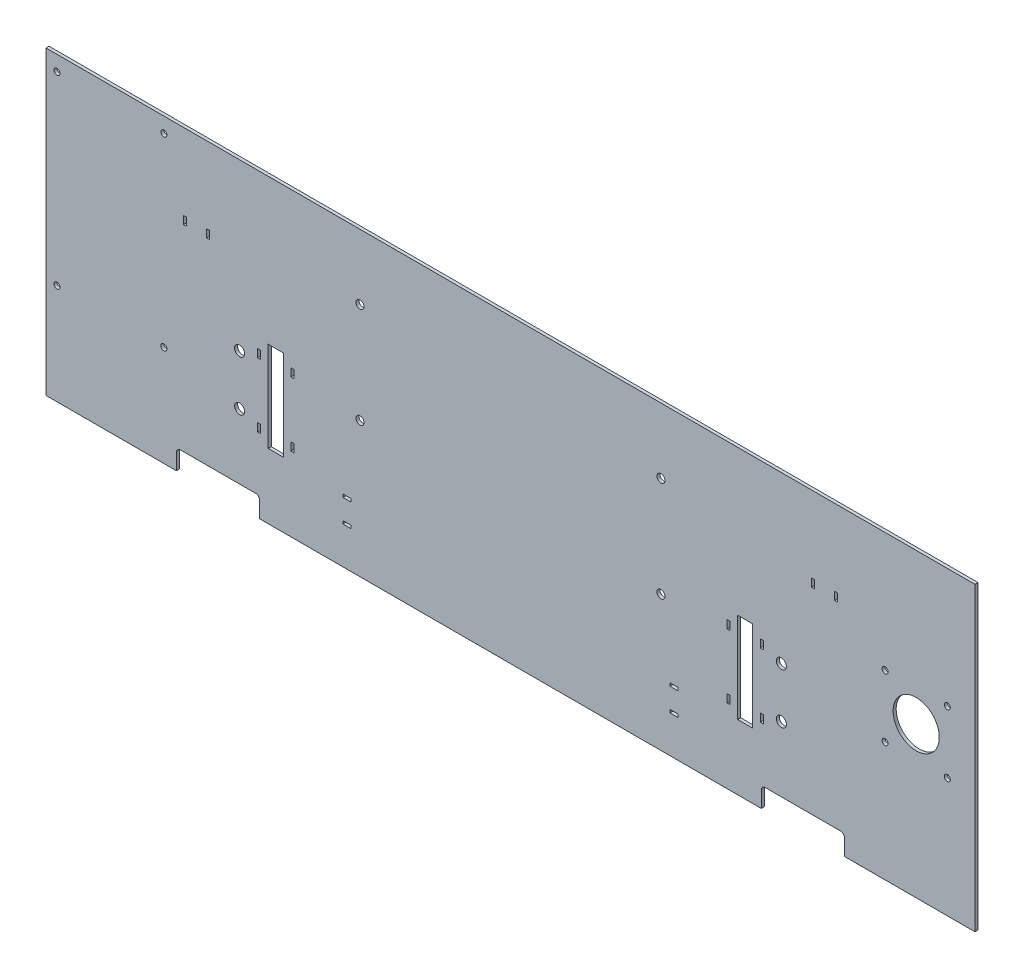
SolidWorks part; units mm, degrees
material "5052-H32"
ref_plane "Front Plane" through (0, 0, 0) normal (0, 0, 1) x (1, 0, 0)
ref_plane "Top Plane" through (0, 0, 0) normal (0, 1, 0) x (1, 0, 0)
ref_plane "Right Plane" through (0, 0, 0) normal (1, 0, 0) x (0, 0, -1)
sketch "Sketch1" plane through (0, 0, 0) normal (0, 0, 1) x (1, 0, 0)
  line L1 (-231.5, 75) -> (231.5, 75)
  line L2 (-231.5, 75) -> (-231.5, -75)
  line L3 (-231.5, -75) -> (231.5, -75)
  line L4 (231.5, 75) -> (231.5, -75)
  line L5 (0, -75) -> (0, 75) construction
  line L6 (-231.5, 0) -> (231.5, 0) construction
  point P480 (0, 0)
  dimension "D1" = 463
  dimension "D2" = 150
base flange "Base-Flange1" sketch "Sketch1" thickness 1.5189 reverse thickness direction no parameters "D1"=0.381
sketch "Sketch48" plane through (0, 0, -1.5189) normal (0, 0, -1) x (-1, 0, 0)
  line L0 (-231.119, 75) -> (-231.119, -75) construction
  line L1 (-231.119, 73.1001) -> (231.119, 73.1001) construction
  line L2 (0, 0) -> (-50000, 0) construction
  line L3 (0, 0) -> (0, -50000) construction
  line L4 (120.75, -42.5) -> (113.25, -42.5)
  line L5 (-120.75, 2.5) -> (-113.25, 2.5)
  line L6 (-120.75, 2.5) -> (-120.75, -42.5)
  line L7 (-120.75, -42.5) -> (-113.25, -42.5)
  line L8 (-113.25, 15) -> (-120.75, 15) construction
  line L9 (-113.25, -9) -> (-113.25, 15) construction
  line L10 (-120.75, -9) -> (-113.25, -9) construction
  line L11 (-120.75, 15) -> (-120.75, -9) construction
  line L12 (-113.25, 2.5) -> (-113.25, -42.5)
  line L13 (-120.75, 2.5) -> (-113.25, -42.5) construction
  line L14 (-120.75, -42.5) -> (-113.25, 2.5) construction
  line L15 (113.25, 2.5) -> (113.25, -42.5)
  line L16 (-120.75, -55) -> (-113.25, -55) construction
  line L17 (-120.75, -31) -> (-120.75, -55) construction
  line L18 (-113.25, -31) -> (-120.75, -31) construction
  line L19 (-113.25, -55) -> (-113.25, -31) construction
  line L20 (120.75, -42.5) -> (113.25, 2.5) construction
  line L21 (120.75, 2.5) -> (113.25, -42.5) construction
  line L22 (120.75, 2.5) -> (120.75, -42.5)
  line L23 (120.75, 2.5) -> (113.25, 2.5)
  line L24 (-109.5, -6) -> (-108, -6)
  line L25 (-109.5, -2) -> (-109.5, -6)
  line L26 (-108, -2) -> (-109.5, -2)
  line L27 (-108, -6) -> (-108, -2)
  line L32 (-124.5, 8) -> (-124.5, 12) construction
  line L33 (-126, 8) -> (-124.5, 8) construction
  line L34 (-126, 12) -> (-126, 8) construction
  line L35 (-124.5, 12) -> (-126, 12) construction
  line L40 (-126, -2) -> (-126, -6)
  line L41 (-124.5, -2) -> (-126, -2)
  line L42 (-124.5, -6) -> (-124.5, -2)
  line L43 (-126, -6) -> (-124.5, -6)
  line L48 (-109.5, 12) -> (-109.5, 8) construction
  line L49 (-108, 12) -> (-109.5, 12) construction
  line L50 (-108, 8) -> (-108, 12) construction
  line L51 (-109.5, 8) -> (-108, 8) construction
  line L56 (-124.5, -38) -> (-124.5, -34)
  line L57 (-126, -38) -> (-124.5, -38)
  line L58 (-126, -34) -> (-126, -38)
  line L59 (-124.5, -34) -> (-126, -34)
  line L64 (-109.5, -34) -> (-109.5, -38)
  line L65 (-108, -34) -> (-109.5, -34)
  line L66 (-108, -38) -> (-108, -34)
  line L67 (-109.5, -38) -> (-108, -38)
  line L72 (-109.5, -52) -> (-108, -52) construction
  line L73 (-109.5, -48) -> (-109.5, -52) construction
  line L74 (-108, -48) -> (-109.5, -48) construction
  line L75 (-108, -52) -> (-108, -48) construction
  line L80 (-126, -48) -> (-126, -52) construction
  line L81 (-124.5, -48) -> (-126, -48) construction
  line L82 (-124.5, -52) -> (-124.5, -48) construction
  line L83 (-126, -52) -> (-124.5, -52) construction
  line L88 (-79.5, -45) -> (-79.5, -43.5)
  line L89 (-83.5, -45) -> (-79.5, -45)
  line L90 (-83.5, -43.5) -> (-83.5, -45)
  line L91 (-79.5, -43.5) -> (-83.5, -43.5)
  line L96 (-79.5, -56.5) -> (-79.5, -55)
  line L97 (-83.5, -56.5) -> (-79.5, -56.5)
  line L98 (-83.5, -55) -> (-83.5, -56.5)
  line L99 (-79.5, -55) -> (-83.5, -55)
  line L104 (-151.5, 33) -> (-150, 33)
  line L105 (-151.5, 37) -> (-151.5, 33)
  line L106 (-150, 37) -> (-151.5, 37)
  line L107 (-150, 33) -> (-150, 37)
  line L112 (-163, 33) -> (-161.5, 33)
  line L113 (-163, 37) -> (-163, 33)
  line L114 (-161.5, 37) -> (-163, 37)
  line L115 (-161.5, 33) -> (-161.5, 37)
  line L120 (113.25, 15) -> (113.25, -9) construction
  line L121 (120.75, 15) -> (113.25, 15) construction
  line L122 (120.75, -9) -> (120.75, 15) construction
  line L123 (113.25, -9) -> (120.75, -9) construction
  line L128 (113.25, -55) -> (120.75, -55) construction
  line L129 (113.25, -31) -> (113.25, -55) construction
  line L130 (120.75, -31) -> (113.25, -31) construction
  line L131 (120.75, -55) -> (120.75, -31) construction
  line L136 (124.5, -34) -> (124.5, -38)
  line L137 (126, -34) -> (124.5, -34)
  line L138 (126, -38) -> (126, -34)
  line L139 (124.5, -38) -> (126, -38)
  line L144 (108, -48) -> (108, -52) construction
  line L145 (109.5, -48) -> (108, -48) construction
  line L146 (109.5, -52) -> (109.5, -48) construction
  line L147 (108, -52) -> (109.5, -52) construction
  line L152 (109.5, -38) -> (109.5, -34)
  line L153 (108, -38) -> (109.5, -38)
  line L154 (108, -34) -> (108, -38)
  line L155 (109.5, -34) -> (108, -34)
  line L160 (124.5, -52) -> (126, -52) construction
  line L161 (124.5, -48) -> (124.5, -52) construction
  line L162 (126, -48) -> (124.5, -48) construction
  line L489 (126, -52) -> (126, -48) construction
  line L494 (83.5, -45) -> (83.5, -43.5)
  line L495 (79.5, -45) -> (83.5, -45)
  line L496 (79.5, -43.5) -> (79.5, -45)
  line L497 (83.5, -43.5) -> (79.5, -43.5)
  line L502 (83.5, -55) -> (79.5, -55)
  line L503 (83.5, -56.5) -> (83.5, -55)
  line L504 (79.5, -56.5) -> (83.5, -56.5)
  line L505 (79.5, -55) -> (79.5, -56.5)
  line L510 (163, 37) -> (161.5, 37)
  line L511 (163, 33) -> (163, 37)
  line L512 (161.5, 33) -> (163, 33)
  line L513 (161.5, 37) -> (161.5, 33)
  line L518 (150, 37) -> (150, 33)
  line L519 (151.5, 37) -> (150, 37)
  line L520 (151.5, 33) -> (151.5, 37)
  line L521 (150, 33) -> (151.5, 33)
  line L526 (109.5, 8) -> (109.5, 12) construction
  line L527 (108, 8) -> (109.5, 8) construction
  line L528 (108, 12) -> (108, 8) construction
  line L529 (109.5, 12) -> (108, 12) construction
  line L534 (108, -2) -> (108, -6)
  line L535 (109.5, -2) -> (108, -2)
  line L536 (109.5, -6) -> (109.5, -2)
  line L537 (108, -6) -> (109.5, -6)
  line L542 (124.5, -2) -> (124.5, -6)
  line L543 (126, -2) -> (124.5, -2)
  line L544 (126, -6) -> (126, -2)
  line L545 (124.5, -6) -> (126, -6)
  line L550 (126, 8) -> (126, 12) construction
  line L551 (124.5, 8) -> (126, 8) construction
  line L552 (124.5, 12) -> (124.5, 8) construction
  line L553 (126, 12) -> (124.5, 12) construction
  circle A2 centre (-186.715, -15.5) radius 1.5
  circle A4 centre (-186.715, 15.5) radius 1.5
  circle A6 centre (-217.715, 15.5) radius 1.5
  circle A17 centre (-202.215, 0) radius 11.5
  circle A24 centre (-217.715, -15.5) radius 1.5
  circle A26 centre (-135, -7.5) radius 2.5
  circle A28 centre (-135, -32.5) radius 2.5
  circle A30 centre (-75, -7.5) radius 2
  circle A32 centre (-75, 42.5) radius 2
  circle A34 centre (135, -32.5) radius 2.5
  circle A36 centre (135, -7.5) radius 2.5
  circle A38 centre (75, -7.5) radius 2
  circle A40 centre (75, 42.5) radius 2
  circle A42 centre (172.7419, -24.8359) radius 1.5
  circle A44 centre (226.0189, -24.8359) radius 1.5
  circle A46 centre (172.7419, 67.4811) radius 1.5
  circle A47 centre (226.0189, 67.4811) radius 1.5
  point P14 (-117, -20)
  dimension "D1" = 23
  dimension "D2" = 3
  dimension "D3" = 5
  dimension "D4" = 4
  dimension "D7" = 202.215
  dimension "D5" = 24
  dimension "D6" = 7.5
  dimension "D8" = 113.25
  dimension "D9" = 22
  dimension "D10" = 15
  dimension "D11" = 8
  dimension "D12" = 2
  dimension "D13" = 7.5
  dimension "D14" = 33
  dimension "D15" = 50
  dimension "D16" = 15.5
  dimension "D17" = 31
  dimension "D18" = 3
  dimension "D19" = 43.5
  dimension "D20" = 14
  dimension "D21" = 32.5
  dimension "D22" = 67.4811
  dimension "D23" = 92.317
  dimension "D24" = 4
  dimension "D25" = 1.5
  dimension "D26" = 75
  dimension "D27" = 79.5
  dimension "D28" = 3.75
  dimension "D29" = 113.25
  dimension "D30" = 15
  dimension "D31" = 135
  dimension "D32" = 150
  dimension "D33" = 11.5
  dimension "D34" = 172.7419
  dimension "D35" = 150
  dimension "D36" = 53.277
  dimension "D37" = 31
  dimension "D38" = 15.5
  dimension "D39" = 15
  dimension "D40" = 3.75
  dimension "D41" = 79.5
  dimension "D42" = 14.25
  dimension "D43" = 150
  dimension "D44" = 11.5
  dimension "D45" = 7.5
  dimension "D46" = 113.25
  dimension "D47" = 45
  dimension "D48" = 70
  dimension "D49" = 20
extrude "Cut-Extrude1" cut sketch "Sketch48" against normal blind 1.5189 contours A44 | A42 | L120 L123 L122 L121 | A36 | L550 L553 L552 L551 | L542 L545 L544 L543 | L534 L537 L536 L535 | L526 L529 L528 L527 | A34 | L136 L139 L138 L137 | L128 L131 L130 L129 | L152 L155 L154 L153 | L144 L147 L146 L145 | L160 L489 L162 L161 | L494 L497 L496 L495 | L502 L505 L504 L503 | L510 L513 L512 L511 | A40 | A38 | L88 L91 L90 L89 | L96 L99 L98 L97 | L16 L19 L18 L17 | L64 L67 L66 L65 | L72 L75 L74 L73 | L80 L83 L82 L81 | L56 L59 L58 L57 | A28 | A26 | A30 | A32 | L8 L11 L10 L9 | L40 L43 L42 L41 | L32 L35 L34 L33 | L48 L51 L50 L49 | L24 L27 L26 L25 | L112 L115 L114 L113 | L104 L107 L106 L105 | A4 | A2 | A24 | A6 | A17 | A47 | A46 | L12 L5 L6 L7 | L22 L23 L15 L4 | L520 L519 L518 L521 normal cut yes
sketch "Sketch50" plane through (0, 0, 0) normal (0, 0, 1) x (1, 0, 0)
  line L0 (125, -75) -> (166.5, -75)
  line L1 (-125, -75) -> (-166.5, -75)
  line L2 (0, 0) -> (0, -75) construction
  line L424 (-166.5, -75) -> (-166.5, -67)
  line L425 (-164.5, -65) -> (-127, -65)
  line L426 (-125, -67) -> (-125, -75)
  line L448 (125, -75) -> (125, -67)
  line L449 (127, -65) -> (164.5, -65)
  line L450 (166.5, -67) -> (166.5, -75)
  arc A17 (-164.5, -65) -> (-166.5, -67) centre (-164.5, -67) ccw
  arc A18 (-125, -67) -> (-127, -65) centre (-127, -67) ccw
  arc A19 (127, -65) -> (125, -67) centre (127, -67) ccw
  arc A20 (166.5, -67) -> (164.5, -65) centre (164.5, -67) ccw
  dimension "D4" = 2
  dimension "D1" = 41.5
  dimension "D2" = 125
  dimension "D3" = 10
  dimension "D5" = 125
  dimension "D6" = 75
extrude "Cut-Extrude3" cut sketch "Sketch50" against normal blind 10 contours L450 A20 L449 A19 L448 L0 | L426 A18 L425 A17 L424 L1
edge flange "Edge-Flange1" [suppressed] sketch "Sketch10" flange profiles "Sketch10", "Sketch11" flange angle 90 flange position material outside bend radius 0.381 thickness 1.5189
sketch "Sketch10" plane through (231.5, 0, 0) normal (1, 0, 0) x (0, 1, 0)
  line L2 (-75, 0) -> (-75, 425)
  line L3 (-75, 425) -> (75, 425)
  line L4 (75, 425) -> (75, 0)
  line L7 (-75, 0) -> (75, 0) construction
  line L8 (-75, 0) -> (75, 0)
sketch "Sketch11" plane through (-231.5, 0, 0) normal (-1, 0, 0) x (0, -1, 0)
  line L2 (-75, 0) -> (-75, 425)
  line L3 (-75, 425) -> (75, 425)
  line L4 (75, 425) -> (75, 0)
  line L5 (-75, 0) -> (75, 0) construction
  line L6 (-75, 0) -> (75, 0)
bend "EdgeBend1" bend radius 0.381 bend angle 90 parameters "D5"=1
bend "EdgeBend2" bend radius 0.381 bend angle 90 parameters "D5"=2, "D6"=10, "D7"=425
edge flange "Edge-Flange2" [suppressed] sketch "Sketch16" flange profiles "Sketch16", "Sketch17" flange angle 90 flange position material inside bend radius 0.381 thickness 1.5189
sketch "Sketch16" plane through (231.5, 0, 425) normal (0, 0, 1) x (0, 1, 0)
  line L0 (75, 0) -> (-75, 0) construction
  line L1 (75, 0) -> (-75, 0)
  line L2 (-75, 0) -> (-75, 231.3811)
  line L3 (-75, 231.3811) -> (75, 231.3811)
  line L4 (75, 231.3811) -> (75, 0)
sketch "Sketch17" plane through (-231.5, 0, 425) normal (0, 0, 1) x (0, -1, 0)
  line L0 (75, 0) -> (-75, 0) construction
  line L1 (75, 0) -> (-75, 0)
  line L2 (-75, 0) -> (-75, 231.3811)
  line L3 (-75, 231.3811) -> (75, 231.3811)
  line L4 (75, 231.3811) -> (75, 0)
bend "EdgeBend3" bend radius 0.381 bend angle 90 parameters "D5"=3
bend "EdgeBend4" bend radius 0.381 bend angle 90 parameters "D5"=4, "D6"=10, "D7"=232.9
sketch "Sketch49" [suppressed] plane through (233.0189, 0, 0) normal (1, 0, 0) x (0, 0, -1)
  line L2 (-425, 75) -> (-425, -75) construction
  line L3 (-378.715, 0) -> (-425, 0) construction
  line L4 (-408.715, 35) -> (-408.715, -35)
  line L5 (-378.715, -35) -> (-378.715, 35)
  arc A1 (-408.715, -35) -> (-378.715, -35) centre (-393.715, -35) ccw
  arc A4 (-408.715, -35) -> (-378.715, -35) centre (-393.715, -35) ccw
  arc A5 (-378.715, 35) -> (-408.715, 35) centre (-393.715, 35) ccw
  dimension "D3" = 70
  dimension "D1" = 16.285
  dimension "D2" = 30
extrude "Cut-Extrude2" [suppressed] cut sketch "Sketch49" against normal through all contours L5 A5 L4 A1 | L3 L5 A5 L4
edge flange "Edge-Flange3" [suppressed] sketch "Sketch38" flange profiles "Sketch38", "Sketch39", "Sketch40", "Sketch41", "Sketch42", "Sketch43", "Sketch44", "Sketch45", "Sketch46", "Sketch47" flange angle 90 flange position material inside bend radius 0.381 thickness 1.5189
sketch "Sketch38" plane through (0, 75, 423.4811) normal (0, 1, 0) x (1, 0, 0)
  line L0 (231.119, 0) -> (0.1189, 0) construction
  line L1 (231.119, 0) -> (0.1189, 0)
  line L2 (0.1189, 0) -> (0.1189, 11.1811)
  line L3 (0.1189, 11.1811) -> (231.119, 11.1811)
  line L4 (231.119, 11.1811) -> (231.119, 0)
sketch "Sketch39" plane through (0, 75, 423.4811) normal (0, 1, 0) x (1, 0, 0)
  line L0 (-0.1189, 0) -> (-231.119, 0) construction
  line L1 (-0.1189, 0) -> (-231.119, 0)
  line L2 (-231.119, 0) -> (-231.119, 11.1811)
  line L3 (-231.119, 11.1811) -> (-0.1189, 11.1811)
  line L4 (-0.1189, 11.1811) -> (-0.1189, 0)
sketch "Sketch40" plane through (-231.5, 75, 0) normal (0, 1, 0) x (0, 0, 1)
  line L0 (423.1001, 0) -> (0.381, 0) construction
  line L1 (423.1001, 0) -> (0.381, 0)
  line L2 (0.381, 0) -> (0.381, 11.1811)
  line L3 (0.381, 11.1811) -> (423.1001, 11.1811)
  line L4 (423.1001, 11.1811) -> (423.1001, 0)
sketch "Sketch41" plane through (231.5, 75, 0) normal (0, 1, 0) x (0, 0, -1)
  line L0 (-0.381, 0) -> (-423.1001, 0) construction
  line L1 (-0.381, 0) -> (-423.1001, 0)
  line L2 (-423.1001, 0) -> (-423.1001, 11.1811)
  line L3 (-423.1001, 11.1811) -> (-0.381, 11.1811)
  line L4 (-0.381, 11.1811) -> (-0.381, 0)
sketch "Sketch42" plane through (0, -75, 423.4811) normal (0, -1, 0) x (-1, 0, 0)
  line L0 (-0.1189, 0) -> (-231.119, 0) construction
  line L1 (-0.1189, 0) -> (-231.119, 0)
  line L2 (-231.119, 0) -> (-231.119, 11.1811)
  line L3 (-231.119, 11.1811) -> (-0.1189, 11.1811)
  line L4 (-0.1189, 11.1811) -> (-0.1189, 0)
sketch "Sketch43" plane through (231.5, -75, 0) normal (0, -1, 0) x (0, 0, 1)
  line L0 (423.1001, 0) -> (0.381, 0) construction
  line L1 (423.1001, 0) -> (0.381, 0)
  line L2 (0.381, 0) -> (0.381, 11.1811)
  line L3 (0.381, 11.1811) -> (423.1001, 11.1811)
  line L4 (423.1001, 11.1811) -> (423.1001, 0)
sketch "Sketch44" plane through (0, -75, 423.4811) normal (0, -1, 0) x (-1, 0, 0)
  line L0 (231.119, 0) -> (0.1189, 0) construction
  line L1 (231.119, 0) -> (0.1189, 0)
  line L2 (0.1189, 0) -> (0.1189, 11.1811)
  line L3 (0.1189, 11.1811) -> (231.119, 11.1811)
  line L4 (231.119, 11.1811) -> (231.119, 0)
sketch "Sketch45" plane through (-231.5, -75, 0) normal (0, -1, 0) x (0, 0, -1)
  line L0 (-0.381, 0) -> (-423.1001, 0) construction
  line L1 (-0.381, 0) -> (-423.1001, 0)
  line L2 (-423.1001, 0) -> (-423.1001, 11.1811)
  line L3 (-423.1001, 11.1811) -> (-0.381, 11.1811)
  line L4 (-0.381, 11.1811) -> (-0.381, 0)
sketch "Sketch46" plane through (0, -75, -1.5189) normal (0, 1, 0) x (1, 0, 0)
  line L1 (231.119, 0) -> (166.5, 0) construction
  line L2 (166.5, 0) -> (166.5, 11.1811)
  line L3 (166.5, 11.1811) -> (231.119, 11.1811)
  line L4 (231.119, 11.1811) -> (231.119, 0)
  line L5 (231.119, 0) -> (166.5, 0)
sketch "Sketch47" plane through (0, 75, -1.5189) normal (0, -1, 0) x (-1, 0, 0)
  line L1 (231.119, 0) -> (-231.119, 0) construction
  line L2 (-231.119, 0) -> (-231.119, 11.1811)
  line L3 (-231.119, 11.1811) -> (231.119, 11.1811)
  line L4 (231.119, 11.1811) -> (231.119, 0)
  line L5 (231.119, 0) -> (-231.119, 0)
bend "EdgeBend5" bend radius 0.381 bend angle 90 parameters "D5"=5
bend "EdgeBend6" bend radius 0.381 bend angle 90 parameters "D5"=6
bend "EdgeBend7" bend radius 0.381 bend angle 90 parameters "D5"=7
bend "EdgeBend8" bend radius 0.381 bend angle 90 parameters "D5"=8
bend "EdgeBend9" bend radius 0.381 bend angle 90 parameters "D5"=9
bend "EdgeBend10" bend radius 0.381 bend angle 90 parameters "D5"=10
bend "EdgeBend11" bend radius 0.381 bend angle 90 parameters "D5"=11
bend "EdgeBend12" bend radius 0.381 bend angle 90 parameters "D5"=12
bend "EdgeBend13" bend radius 0.381 bend angle 90 parameters "D5"=13
bend "EdgeBend14" bend radius 0.381 bend angle 90 parameters "D5"=14, "D6"=10, "D7"=12.7
fillet "Fillet1" [suppressed] radius 2
sketch "Bend-Lines1" [suppressed] plane through (0, 0, 0) normal (0, 1, 0) x (1, 0, 0)
sketch "Bounding-Box1" [suppressed] plane through (0, 0, 0) normal (0, 1, 0) x (1, 0, 0)
sheet metal parameters "Sheet-Metal1" thickness 1.5189 parameters "D1"=1.905
flat pattern "Flat-Pattern1" [suppressed]
sketch "Bend-Lines2" plane through (0, 0, 0) normal (0, 1, 0) x (1, 0, 0)
sketch3d "Bounding-Box2" [suppressed]
  line L0 (231.5, -75, 0) -> (-231.5, -75, 0) construction
  line L1 (231.5, 75, 0) -> (-231.5, 75, 0) construction
  line L2 (231.5, -75, 0) -> (231.5, 75, 0) construction
  line L3 (-231.5, -75, 0) -> (-231.5, 75, 0) construction
sheet metal parameters "Sheet-Metal2" thickness 1.5189 parameters "D1"=1.905
flat pattern "Flat-Pattern1"
sketch "Bend-Lines2" plane through (0, 0, 0) normal (0, 0, 1) x (1, 0, 0)
  line L0 (-230.1687, 75) -> (-230.1687, -75) construction
  line L1 (230.1687, -75) -> (230.1687, 75) construction
  line L2 (-230.1687, 75) -> (-230.1687, -75) construction
  line L3 (230.1687, -75) -> (230.1687, 75) construction
sketch3d "Bounding-Box2" [suppressed]
  line L0 (-655.3564, -75, 0) -> (655.3564, -75, 0) construction
  line L1 (-655.3564, 75, 0) -> (655.3564, 75, 0) construction
  line L2 (-655.3564, -75, 0) -> (-655.3564, 75, 0) construction
  line L3 (655.3564, -75, 0) -> (655.3564, 75, 0) construction
bend of the flat pattern "Flatten-<EdgeBend1>1"
bend of the flat pattern "Flatten-<EdgeBend2>1"
sheet metal parameters "Sheet-Metal3" thickness 1.5189 parameters "D1"=1.905
flat pattern "Flat-Pattern1"
sketch "Bend-Lines2" plane through (0, 0, 0) normal (0, 0, 1) x (1, 0, 0)
  line L0 (-230.1687, 75) -> (-230.1687, -75) construction
  line L1 (230.1687, -75) -> (230.1687, 75) construction
  line L2 (-230.1687, 75) -> (-230.1687, -75) construction
  line L3 (230.1687, -75) -> (230.1687, 75) construction
  line L4 (-654.0251, 75) -> (-654.0251, -75) construction
  line L5 (654.0251, -75) -> (654.0251, 75) construction
  line L6 (-654.0251, 75) -> (-654.0251, -75) construction
  line L7 (654.0251, -75) -> (654.0251, 75) construction
sketch3d "Bounding-Box2" [suppressed]
  line L0 (-884.1439, -75, 0) -> (884.1439, -75, 0) construction
  line L1 (-884.1439, 75, 0) -> (884.1439, 75, 0) construction
  line L2 (-884.1439, -75, 0) -> (-884.1439, 75, 0) construction
  line L3 (884.1439, -75, 0) -> (884.1439, 75, 0) construction
bend of the flat pattern "Flatten-<EdgeBend1>1"
bend of the flat pattern "Flatten-<EdgeBend2>1"
bend of the flat pattern "Flatten-<EdgeBend3>1"
bend of the flat pattern "Flatten-<EdgeBend4>1"
sheet metal parameters "Sheet-Metal4" thickness 1.5189 parameters "D1"=1.905
flat pattern "Flat-Pattern1"
sketch "Bend-Lines2" plane through (0, 0, 0) normal (0, 0, 1) x (1, 0, 0)
  line L0 (-230.1687, -75) -> (-230.1687, 75) construction
  line L1 (230.1687, 75) -> (230.1687, -75) construction
  line L2 (-230.1687, -75) -> (-230.1687, 75) construction
  line L3 (230.1687, 75) -> (230.1687, -75) construction
  line L4 (-654.0251, -75) -> (-654.0251, 75) construction
  line L5 (654.0251, 75) -> (654.0251, -75) construction
  line L6 (-654.0251, -75) -> (-654.0251, 75) construction
  line L7 (654.0251, 75) -> (654.0251, -75) construction
  line L8 (228.0761, 73.6687) -> (-228.0761, 73.6687) construction
  line L9 (-228.0761, -73.6687) -> (228.0761, -73.6687) construction
  line L10 (-651.5789, -73.6687) -> (-232.2614, -73.6687) construction
  line L11 (-884.1439, -73.6687) -> (-656.4714, -73.6687) construction
  line L12 (232.2614, -73.6687) -> (651.5789, -73.6687) construction
  line L13 (656.4714, -73.6687) -> (884.1439, -73.6687) construction
  line L14 (651.5789, 73.6687) -> (232.2614, 73.6687) construction
  line L15 (-232.2614, 73.6687) -> (-651.5789, 73.6687) construction
  line L16 (-656.4714, 73.6687) -> (-884.1439, 73.6687) construction
  line L17 (884.1439, 73.6687) -> (656.4714, 73.6687) construction
  line L18 (228.0761, 73.6687) -> (-228.0761, 73.6687) construction
  line L19 (-228.0761, -73.6687) -> (228.0761, -73.6687) construction
  line L20 (-651.5789, -73.6687) -> (-232.2614, -73.6687) construction
  line L21 (-884.1439, -73.6687) -> (-656.4714, -73.6687) construction
  line L22 (232.2614, -73.6687) -> (651.5789, -73.6687) construction
  line L23 (656.4714, -73.6687) -> (884.1439, -73.6687) construction
  line L24 (651.5789, 73.6687) -> (232.2614, 73.6687) construction
  line L25 (-232.2614, 73.6687) -> (-651.5789, 73.6687) construction
  line L26 (-656.4714, 73.6687) -> (-884.1439, 73.6687) construction
  line L27 (884.1439, 73.6687) -> (656.4714, 73.6687) construction
sketch3d "Bounding-Box2" [suppressed]
  line L0 (-884.1439, -85.0375, 0) -> (884.1439, -85.0375, 0) construction
  line L1 (-884.1439, 85.0375, 0) -> (884.1439, 85.0375, 0) construction
  line L2 (-884.1439, -85.0375, 0) -> (-884.1439, 85.0375, 0) construction
  line L3 (884.1439, -85.0375, 0) -> (884.1439, 85.0375, 0) construction
bend of the flat pattern "Flatten-<EdgeBend1>1"
bend of the flat pattern "Flatten-<EdgeBend2>1"
bend of the flat pattern "Flatten-<EdgeBend3>1"
bend of the flat pattern "Flatten-<EdgeBend4>1"
bend of the flat pattern "Flatten-<EdgeBend5>1"
bend of the flat pattern "Flatten-<EdgeBend6>1"
bend of the flat pattern "Flatten-<EdgeBend7>1"
bend of the flat pattern "Flatten-<EdgeBend8>1"
bend of the flat pattern "Flatten-<EdgeBend9>1"
bend of the flat pattern "Flatten-<EdgeBend10>1"
bend of the flat pattern "Flatten-<EdgeBend11>1"
bend of the flat pattern "Flatten-<EdgeBend12>1"
bend of the flat pattern "Flatten-<EdgeBend13>1"
bend of the flat pattern "Flatten-<EdgeBend14>1"
sheet metal parameters "Sheet-Metal5" thickness 1.5189 parameters "D1"=1.905
flat pattern "Flat-Pattern1"
sketch "Bend-Lines2" plane through (0, 0, 0) normal (0, 0, 1) x (1, 0, 0)
  line L0 (-232.0147, 73.1001) -> (-232.0147, -73.1001) construction
  line L1 (232.0147, -73.1001) -> (232.0147, 73.1001) construction
  line L2 (-232.0147, 73.1001) -> (-232.0147, -73.1001) construction
  line L3 (232.0147, -73.1001) -> (232.0147, 73.1001) construction
  line L4 (-656.5252, 73.1001) -> (-656.5252, -73.1001) construction
  line L5 (656.5252, -73.1001) -> (656.5252, 73.1001) construction
  line L6 (-656.5252, 73.1001) -> (-656.5252, -73.1001) construction
  line L7 (656.5252, -73.1001) -> (656.5252, 73.1001) construction
  line L8 (231.119, 73.9958) -> (-231.119, 73.9958) construction
  line L9 (-231.119, -73.9958) -> (231.119, -73.9958) construction
  line L10 (-655.8181, -73.9958) -> (-232.9104, -73.9958) construction
  line L11 (-888.421, -73.9958) -> (-657.2323, -73.9958) construction
  line L12 (232.9104, -73.9958) -> (655.8181, -73.9958) construction
  line L13 (657.2323, -73.9958) -> (888.421, -73.9958) construction
  line L14 (655.8181, 73.9958) -> (232.9104, 73.9958) construction
  line L15 (-232.9104, 73.9958) -> (-655.8181, 73.9958) construction
  line L16 (-657.2323, 73.9958) -> (-888.421, 73.9958) construction
  line L17 (888.421, 73.9958) -> (657.2323, 73.9958) construction
  line L18 (231.119, 73.9958) -> (-231.119, 73.9958) construction
  line L19 (-231.119, -73.9958) -> (231.119, -73.9958) construction
  line L20 (-655.8181, -73.9958) -> (-232.9104, -73.9958) construction
  line L21 (-888.421, -73.9958) -> (-657.2323, -73.9958) construction
  line L22 (232.9104, -73.9958) -> (655.8181, -73.9958) construction
  line L23 (657.2323, -73.9958) -> (888.421, -73.9958) construction
  line L24 (655.8181, 73.9958) -> (232.9104, 73.9958) construction
  line L25 (-232.9104, 73.9958) -> (-655.8181, 73.9958) construction
  line L26 (-657.2323, 73.9958) -> (-888.421, 73.9958) construction
  line L27 (888.421, 73.9958) -> (657.2323, 73.9958) construction
sketch3d "Bounding-Box2" [suppressed]
  line L0 (-888.421, -85.6916, 0) -> (888.421, -85.6916, 0) construction
  line L1 (-888.421, 85.6916, 0) -> (888.421, 85.6916, 0) construction
  line L2 (-888.421, -85.6916, 0) -> (-888.421, 85.6916, 0) construction
  line L3 (888.421, -85.6916, 0) -> (888.421, 85.6916, 0) construction
bend of the flat pattern "Flatten-<EdgeBend3>1"
bend of the flat pattern "Flatten-<EdgeBend4>1"
sheet metal parameters "Sheet-Metal6" thickness 1.5189 parameters "D1"=1.905
flat pattern "Flat-Pattern1"
sketch "Bend-Lines2" plane through (0, 0, 0) normal (0, 0, 1) x (1, 0, 0)
  line L0 (-232.0147, 75) -> (-232.0147, -75) construction
  line L1 (232.0147, -75) -> (232.0147, 75) construction
  line L2 (-232.0147, 75) -> (-232.0147, -75) construction
  line L3 (232.0147, -75) -> (232.0147, 75) construction
  line L4 (-656.5252, 75) -> (-656.5252, -75) construction
  line L5 (656.5252, -75) -> (656.5252, 75) construction
  line L6 (-656.5252, 75) -> (-656.5252, -75) construction
  line L7 (656.5252, -75) -> (656.5252, 75) construction
  point P8 (231.119, 73.9958)
  point P9 (-231.119, 73.9958)
  point P10 (-231.119, -73.9958)
  point P11 (231.119, -73.9958)
  point P13 (-232.9104, -73.9958)
  point P14 (-888.421, -73.9958)
  point P16 (232.9104, -73.9958)
  point P19 (888.421, -73.9958)
  point P21 (232.9104, 73.9958)
  point P22 (-232.9104, 73.9958)
  point P25 (-888.421, 73.9958)
  point P26 (888.421, 73.9958)
  point P28 (-655.8181, -73.9958)
  point P29 (-657.2323, -73.9958)
  point P30 (655.8181, -73.9958)
  point P31 (657.2323, -73.9958)
  point P32 (655.8181, 73.9958)
  point P33 (-655.8181, 73.9958)
  point P34 (-657.2323, 73.9958)
  point P35 (657.2323, 73.9958)
sketch3d "Bounding-Box2" [suppressed]
  line L0 (-888.421, -75, 0) -> (888.421, -75, 0) construction
  line L1 (-888.421, 75, 0) -> (888.421, 75, 0) construction
  line L2 (-888.421, -75, 0) -> (-888.421, 75, 0) construction
  line L3 (888.421, -75, 0) -> (888.421, 75, 0) construction
bend of the flat pattern "Flatten-<EdgeBend1>1"
bend of the flat pattern "Flatten-<EdgeBend2>1"
bend of the flat pattern "Flatten-<EdgeBend3>1"
bend of the flat pattern "Flatten-<EdgeBend4>1"
sheet metal parameters "Sheet-Metal7" thickness 1.5189 parameters "D1"=1.905
flat pattern "Flat-Pattern1"
sketch "Bend-Lines2" plane through (0, 0, 0) normal (0, 0, 1) x (1, 0, 0)
  point P0 (-232.0147, 73.1001)
  point P1 (-232.0147, -73.1001)
  point P2 (232.0147, -73.1001)
  point P3 (232.0147, 73.1001)
  point P4 (-656.5252, 73.1001)
  point P5 (-656.5252, -73.1001)
  point P6 (656.5252, -73.1001)
  point P7 (656.5252, 73.1001)
  point P8 (231.119, 73.9958)
  point P9 (-231.119, 73.9958)
  point P10 (231.119, -73.9958)
  point P11 (166.5, -73.9958)
  point P12 (-655.8181, -73.9958)
  point P13 (-232.9104, -73.9958)
  point P14 (-888.421, -73.9958)
  point P15 (-657.2323, -73.9958)
  point P16 (232.9104, -73.9958)
  point P17 (655.8181, -73.9958)
  point P18 (657.2323, -73.9958)
  point P19 (888.421, -73.9958)
  point P20 (655.8181, 73.9958)
  point P21 (232.9104, 73.9958)
  point P22 (-232.9104, 73.9958)
  point P23 (-655.8181, 73.9958)
  point P24 (-657.2323, 73.9958)
  point P25 (-888.421, 73.9958)
  point P26 (888.421, 73.9958)
  point P27 (657.2323, 73.9958)
  point P28 (125, -73.9958)
  point P29 (-125, -73.9958)
  point P30 (-166.5, -73.9958)
  point P31 (-231.119, -73.9958)
sketch3d "Bounding-Box2" [suppressed]
  line L0 (-231.5, -75, 0) -> (231.5, -75, 0) construction
  line L1 (-231.5, 75, 0) -> (231.5, 75, 0) construction
  line L2 (-231.5, -75, 0) -> (-231.5, 75, 0) construction
  line L3 (231.5, -75, 0) -> (231.5, 75, 0) construction
